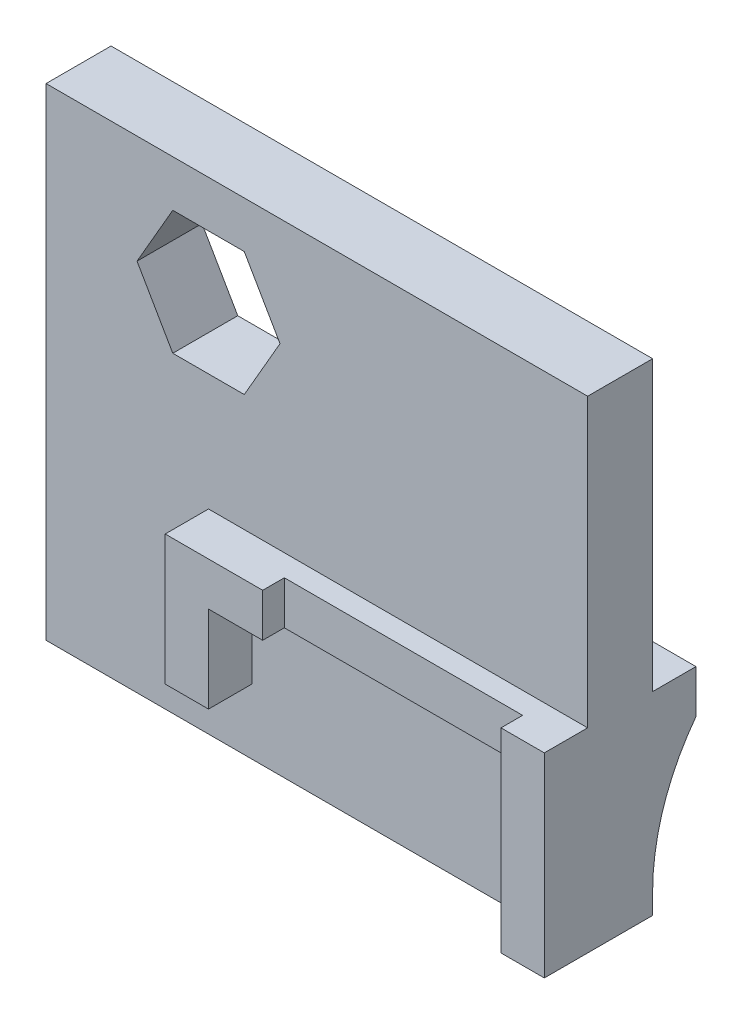
SolidWorks part; units mm, degrees
ref_plane "Plan de face" through (0, 0, 0) normal (0, 0, 1) x (1, 0, 0)
ref_plane "Plan de dessus" through (0, 0, 0) normal (0, 1, 0) x (1, 0, 0)
ref_plane "Plan de droite" through (0, 0, 0) normal (1, 0, 0) x (0, 0, -1)
sketch "Esquisse1" plane through (0, 0, 0) normal (0, 0, 1) x (1, 0, 0)
  line L1 (1.65, -2.8579) -> (3.3, 0)
  line L2 (3.3, 0) -> (1.65, 2.8579)
  line L3 (1.65, 2.8579) -> (-1.65, 2.8579)
  line L4 (-1.65, 2.8579) -> (-3.3, 0)
  line L5 (-3.3, 0) -> (-1.65, -2.8579)
  line L6 (-1.65, -2.8579) -> (1.65, -2.8579)
  line L7 (-7.5, 5) -> (17.5, 5)
  line L8 (-7.5, 5) -> (-7.5, -17.2579)
  line L9 (-7.5, -17.2579) -> (17.5, -17.2579)
  line L10 (17.5, 5) -> (17.5, -17.2579)
  circle A0 centre (0, 0) radius 2.8579 construction
  point P13 (0, 0)
  dimension "D1" = 3.3
  dimension "D2" = 25
  dimension "D3" = 14.4
  dimension "D4" = 5
  dimension "D5" = 17.5
extrude "Boss.-Extru.1" add sketch "Esquisse1" along normal blind 3
sketch "Esquisse2" plane through (0, 0, 0) normal (0, 0, -1) x (-1, 0, 0)
  line L0 (7.5, 5) -> (7.5, -17.2579) construction
  line L1 (7.5, -8.3079) -> (-17.5, -8.3079)
  line L2 (7.5, -8.3079) -> (7.5, -10.3079)
  line L3 (7.5, -10.3079) -> (-17.5, -10.3079)
  line L4 (-17.5, -8.3079) -> (-17.5, -10.3079)
  line L5 (-17.5, -17.2579) -> (-17.5, 5) construction
  line L6 (1.65, -2.8579) -> (-1.65, -2.8579) construction
  dimension "D1" = 5.45
  dimension "D2" = 2
extrude "Boss.-Extru.2" add sketch "Esquisse2" along normal blind 2
sketch "Esquisse3" plane through (0, 0, 3) normal (0, 0, 1) x (1, 0, 0)
  line L0 (17.5, -17.2579) -> (17.5, 5) construction
  line L1 (0, -8.2579) -> (17.5, -8.2579)
  line L2 (0, -8.2579) -> (0, -14.2579)
  line L4 (17.5, -8.2579) -> (17.5, -17.2579)
  line L5 (2, -10.2579) -> (15.5, -10.2579)
  line L6 (2, -10.2579) -> (2, -14.2579)
  line L8 (15.5, -10.2579) -> (15.5, -17.2579)
  line L9 (0, -14.2579) -> (2, -14.2579)
  line L11 (15.5, -17.2579) -> (17.5, -17.2579)
  line L12 (-7.5, -17.2579) -> (17.5, -17.2579) construction
  dimension "D1" = 13.5
  dimension "D2" = 7
  dimension "D3" = 4
  dimension "D4" = 2
  dimension "D5" = 2
  dimension "D6" = 2
extrude "Boss.-Extru.3" add sketch "Esquisse3" along normal blind 2
sketch "Esquisse4" [suppressed] plane through (0, 0, 5) normal (0, 0, 1) x (1, 0, 0)
  line L0 (-5.5, -17.2579) -> (17.5, -17.2579) construction
  line L1 (-3.5, -16.2579) -> (15.5, -16.2579)
  line L2 (-3.5, -16.2579) -> (-3.5, -17.2579)
  line L3 (-3.5, -17.2579) -> (15.5, -17.2579)
  line L4 (15.5, -16.2579) -> (15.5, -17.2579)
  line L5 (15.5, -17.2579) -> (15.5, -9.2579) construction
extrude "Enlèv. mat.-Extru.1" [suppressed] cut sketch "Esquisse4" against normal blind 2
sketch "Esquisse5" plane through (0, 0, 3) normal (0, 0, 1) x (1, 0, 0)
  line L1 (2, -10.2579) -> (-1.3673, -10.2579)
  line L2 (2, -10.2579) -> (2, -15.6051)
  line L3 (2, -15.6051) -> (-1.3673, -15.6051)
  line L4 (-1.3673, -10.2579) -> (-1.3673, -15.6051)
extrude "Boss.-Extru.4" [suppressed] add sketch "Esquisse5" along normal blind 2
sketch "Esquisse6" plane through (0, 0, 5) normal (0, 0, 1) x (1, 0, 0)
  line L5 (17.5, -8.2579) -> (0, -8.2579) construction
  line L6 (4.5, -8.2579) -> (15.5, -8.2579)
  line L7 (4.5, -8.2579) -> (4.5, -10.2579)
  line L8 (4.5, -10.2579) -> (15.5, -10.2579)
  line L9 (15.5, -8.2579) -> (15.5, -10.2579)
  line L10 (15.5, -10.2579) -> (2, -10.2579) construction
  line L11 (2, -10.2579) -> (2, -14.2579) construction
  dimension "D1" = 11
  dimension "D2" = 2.5
extrude "Enlèv. mat.-Extru.2" cut sketch "Esquisse6" against normal blind 1
fillet "Congé1" radius 10 1 edges at (5, -10.3079, 0)
